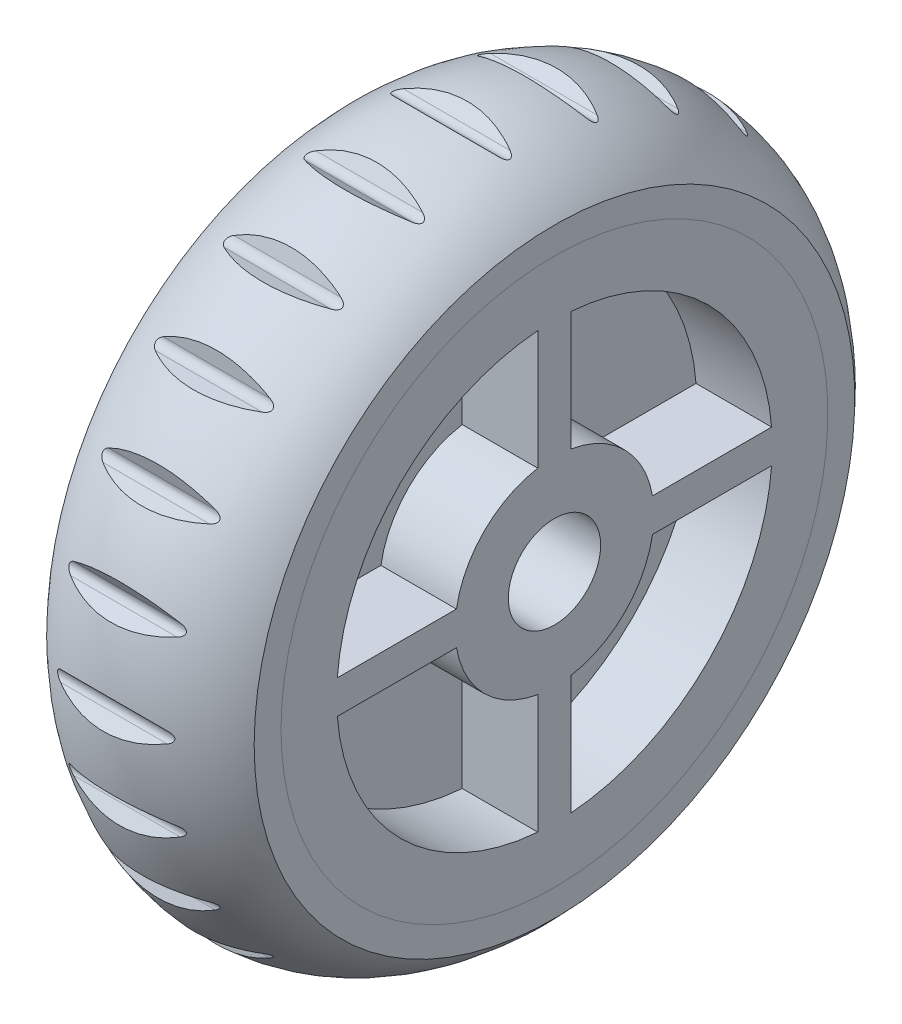
SolidWorks part; units mm, degrees
ref_plane "Front Plane" through (0, 0, 0) normal (0, 0, 1) x (1, 0, 0)
ref_plane "Top Plane" through (0, 0, 0) normal (0, 1, 0) x (1, 0, 0)
ref_plane "Right Plane" through (0, 0, 0) normal (1, 0, 0) x (0, 0, -1)
ref_axis "Axis1" through (3.6322, 0, 0) along (-1, 0, 0)
sketch "Sketch1" plane through (0, 0, 0) normal (0, 0, 1) x (1, 0, 0)
  line L0 (-3.302, 8.7312) -> (3.302, 8.7312)
  line L1 (-3.302, 8.7312) -> (-3.302, 9.5885)
  line L2 (3.302, 9.5885) -> (3.302, 8.7312)
  line L3 (0, 0) -> (0, 6.7733) construction
  line L4 (0, 6.7733) -> (0, 11.1125) construction
  line L5 (-3.302, 9.5885) -> (0, 9.5885) construction
  line L6 (0, 9.5885) -> (3.302, 9.5885) construction
  line L7 (0, 0) -> (7.6886, 0) construction
  arc A0 (-3.302, 9.5885) -> (3.302, 9.5885) centre (0, 6.7733) cw
  point P4 (0, 0)
  dimension "D1" = 6.604
  dimension "D2" = 1.524
  dimension "D3" = 17.4625
  dimension "D4" = 22.225
revolve "Revolve1" add sketch "Sketch1" angle 360 about L7
sketch "Sketch2" plane through (0, 0, 0) normal (1, 0, 0) x (0, 0, -1)
  line L0 (-1.524, 12.1067) -> (-0.1796, 10.7623)
  line L1 (0.1796, 10.7623) -> (1.524, 12.1067)
  line L2 (1.524, 12.1067) -> (-1.524, 12.1067)
  line L3 (0, 0) -> (0, 10.5827) construction
  line L4 (0, 10.5827) -> (0, 12.1067) construction
  arc A0 (-0.1796, 10.7623) -> (0.1796, 10.7623) centre (0, 10.9419) ccw
  circle A1 centre (0, 0) radius 11.1125 construction
  point P12 (0, 11.1125)
  dimension "D3" = 0.254
  dimension "D2" = 0.1706
  dimension "D1" = 1.524
extrude "Cut-Extrude1" cut sketch "Sketch2" against normal through all both and the other way through all
pattern_circular "CirPattern1" count 24 over 360 about axis through (3.6322, 0, 0) along (-1, 0, 0) of "Cut-Extrude1"
shell "Shell2" thickness 0.762 removed face at (3.302, 0, 8.7312)
sketch "Sketch4" plane through (0, 0, 0) normal (1, 0, 0) x (0, 0, -1)
  circle A0 centre (0, 0) radius 8.7312 construction
  circle A1 centre (0, 0) radius 8.7312
extrude "Boss-Extrude1" add sketch "Sketch4" along normal mid plane 6.604 separate body
shell "Shell5" thickness 1.778 removed face at (3.302, 0, -8.7312) removed face at (-3.302, 0, -8.7312)
sketch "Sketch9" plane through (0, 0, 0) normal (1, 0, 0) x (0, 0, -1)
  circle A0 centre (0, 0) radius 6.9532 construction
  circle A1 centre (0, 0) radius 6.9532
extrude "Boss-Extrude2" add sketch "Sketch9" along normal mid plane 1.778
sketch "Sketch5" plane through (0, 0, 0) normal (0, 0, 1) x (1, 0, 0)
  line L0 (2.54, 9.2922) -> (2.54, 8.7312)
  line L1 (2.54, -8.7312) -> (2.54, -9.2922)
  line L3 (2.54, 9.2922) -> (2.54, 8.7312)
  line L6 (0.762, 9.9259) -> (1.6904, 9.9259)
  line L7 (0.762, 8.7312) -> (2.54, 8.7312)
  line L8 (0.762, 9.9259) -> (0.762, 8.7312)
  line L9 (0, 0) -> (5.5712, 0) construction
  arc A0 (-1.6904, 8.3384) -> (-2.54, 7.7047) centre (0, 5.1858) ccw
  arc A1 (2.54, 9.2922) -> (1.6904, 9.9259) centre (0, 6.7733) ccw
  arc A3 (1.6904, -8.3384) -> (2.54, -7.7047) centre (0, -5.1858) ccw
  arc A4 (-2.54, -7.7047) -> (-1.6904, -8.3384) centre (0, -5.1858) ccw
  arc A9 (2.54, 9.2922) -> (1.6904, 9.9259) centre (0, 6.7733) ccw
  dimension "D1" = 1.778
revolve "Revolve2" add sketch "Sketch5" angle 360 about L9
mirror "Mirror1" about plane through (0, 0, 0) normal (1, 0, 0) of "Revolve2"
sketch "Sketch10" plane through (0, 0, 0) normal (1, 0, 0) x (0, 0, -1)
  circle A0 centre (0, 0) radius 3.175
  dimension "D1" = 6.35
extrude "Boss-Extrude3" add sketch "Sketch10" along normal up to surface and the other way up to surface up to face at (3.302, 0, -6.9532) other way up to face at (-3.302, 0, -6.9532)
sketch "Sketch15" plane through (3.302, 0, 0) normal (1, 0, 0) x (0, 0, -1)
  line L0 (0, 0) -> (0, 6.9532)
  circle A0 centre (0, 0) radius 6.9532 construction
rib "Rib1" sketch "Sketch15" sketch "Sketch15" thickness 1.0668 extrusion direction normal to sketch draft on no parameters "D1"=1.0668
pattern_circular "CirPattern2" count 4 over 360 about axis through (3.6322, 0, 0) along (-1, 0, 0) of "Rib1"
mirror "Mirror2" about plane through (0, 0, 0) normal (1, 0, 0) of "CirPattern2"
hole_wizard "#4 Clearance Hole2" positions "Sketch11" profile "Sketch12" hole size "#4" standard "ANSI Inch" end condition through all
sketch "Sketch11" plane through (3.302, 0, 0) normal (1, 0, 0) x (0, 0, -1)
  point P0 (0, 0)
sketch "Sketch12" plane through (3.302, 0, 0) normal (0, 1, 0) x (0, 0, -1)
  line L0 (0, 0) -> (0, 6.604)
  line L1 (0, 6.604) -> (1.4732, 6.604)
  line L2 (1.4732, 6.604) -> (1.4732, 0)
  line L5 (1.4732, 0) -> (0, 0)
  line L11 (0, -6.35) -> (0, 107.95) construction
  dimension "Thru Hole Dia." = 2.9464
  dimension "Thru Hole Depth" = 6.604
